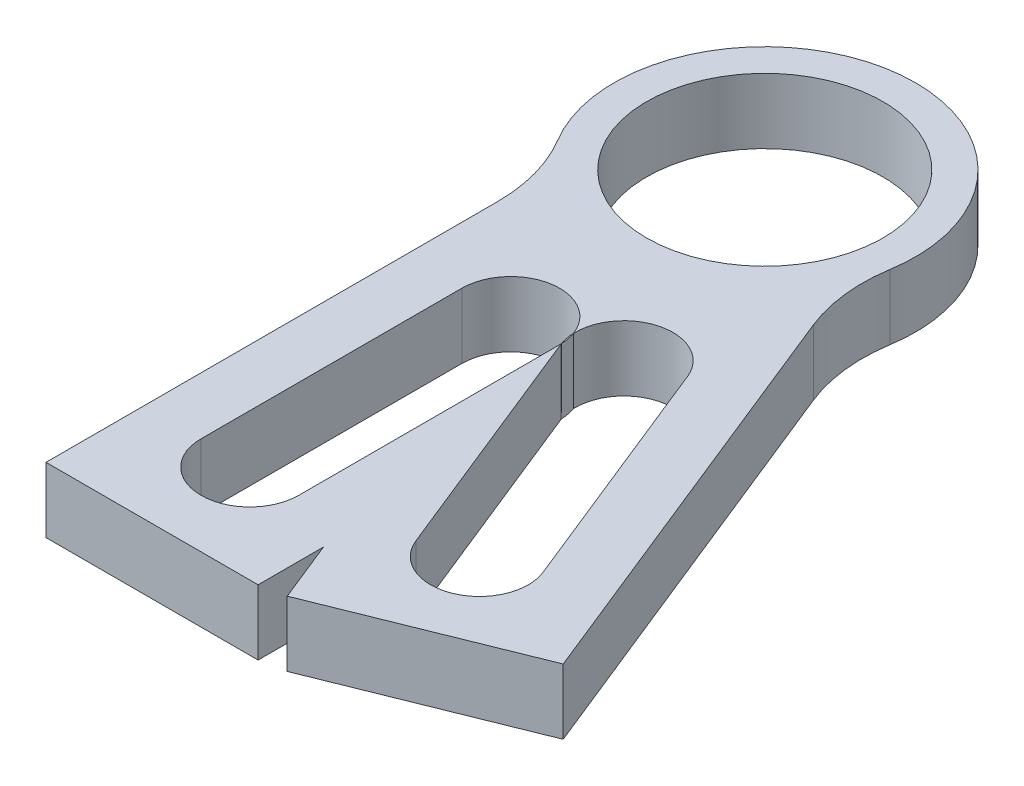
SolidWorks part; units mm, degrees
ref_plane "Front Plane" through (0, 0, 0) normal (0, 0, 1) x (1, 0, 0)
ref_plane "Top Plane" through (0, 0, 0) normal (0, 1, 0) x (1, 0, 0)
ref_plane "Right Plane" through (0, 0, 0) normal (1, 0, 0) x (0, 0, -1)
sketch "Sketch1" plane through (0, 0, 0) normal (0, 1, 0) x (1, 0, 0)
  line L0 (-10.3251, -10.437) -> (10.3251, -10.437)
  line L1 (0, -8.4388) -> (0, 23.3735) construction
  line L2 (-10.3251, -10.437) -> (-10.3251, -59.6596)
  line L3 (-10.3251, -59.6596) -> (10.3251, -59.6596)
  line L4 (10.3251, -59.6596) -> (10.3251, -10.437)
  line L5 (-5.6801, -13.5379) -> (13.4759, -5.8256)
  line L6 (13.4759, -5.8256) -> (31.8593, -51.4866)
  line L7 (31.8593, -51.4866) -> (12.7033, -59.1989)
  line L8 (12.7033, -59.1989) -> (-5.6801, -13.5379)
  line L9 (49.7615, -123.5986) -> (8.9464, -22.2213) construction
  circle A0 centre (0, 0) radius 11.5062
  circle A1 centre (0, 0) radius 14.6812
  point P7 (0, -10.437)
  point P16 (3.8979, -9.6817)
  point P18 (22.2813, -55.3427)
  dimension "D1" = 23.0124
  dimension "D2" = 29.3624
  dimension "D3" = 20.6502
  dimension "D4" = 49.2227
  dimension "D5" = 21.93
  dimension "D6" = 20.6502
  dimension "D7" = 49.2227
extrude "Boss-Extrude1" add sketch "Sketch1" along normal blind 6.35 contours A1 L4 L8 L7 L6 | A1 L8 L4 | A1 L2 L3 L4 L8 | L0 A1 L5 A0 | L5 A1 L0 A0 | L0 A1 L5 A0 | L5 A1 L0 A0 region at (-5.5059, 0, -13.1919) region at (-2.5647, 0, 41.2385) region at (-5.7496, 0, 11.6802) region at (5.2047, 0, 26.8636) region at (2.4413, 0, 12.6006) region at (9.6958, 0, 8.6877) region at (17.7806, 0, 37.2967)
fillet "Fillet1" radius 1.6002 rebuild error yes
fillet "Fillet2" radius 15.875 2 edges at (13.4759, 3.175, 5.8256) (-10.3251, 3.175, 10.437)
sketch "Sketch2" plane through (0, 6.35, 0) normal (0, 1, 0) x (1, 0, 0)
  line L1 (24.8001, -61.5991) -> (-1.9017, 4.7235) construction
  line L2 (31.8593, -51.4866) -> (12.7033, -59.1989) construction
  line L3 (0, -64.2697) -> (0, 5.8755) construction
  line L4 (-4.7625, -50.1346) -> (-4.7625, -24.7346)
  line L5 (4.7625, -24.7346) -> (4.7625, -50.1346)
  line L6 (13.6551, -21.1649) -> (23.1413, -44.7269)
  line L7 (4.8193, -24.7222) -> (14.3055, -48.2843)
  line L8 (-10.3251, -59.6596) -> (10.3251, -59.6596) construction
  circle A0 centre (18.7234, -46.5056) radius 4.7625
  circle A1 centre (9.2372, -22.9435) radius 4.7625
  circle A2 centre (0, -24.7346) radius 4.7625
  circle A3 centre (0, -50.1346) radius 4.7625
  point P5 (22.2813, -55.3427)
  dimension "D1" = 9.525
  dimension "D2" = 25.4
  dimension "D3" = 25.4
  dimension "D4" = 9.525
  dimension "D5" = 9.5264
extrude "Cut-Extrude1" cut sketch "Sketch2" against normal blind 6.35 contours A2 | A3 L5 A2 L4 | A3 | A1 | A1 L7 A0 L6 | A0 region at (0, 6.35, 37.4346) region at (0, 6.35, 50.1346) region at (-0.0074, 6.35, 24.7361) region at (9.2446, 6.35, 22.9421) region at (13.9803, 6.35, 34.7246) region at (18.7234, 6.35, 46.5056)
